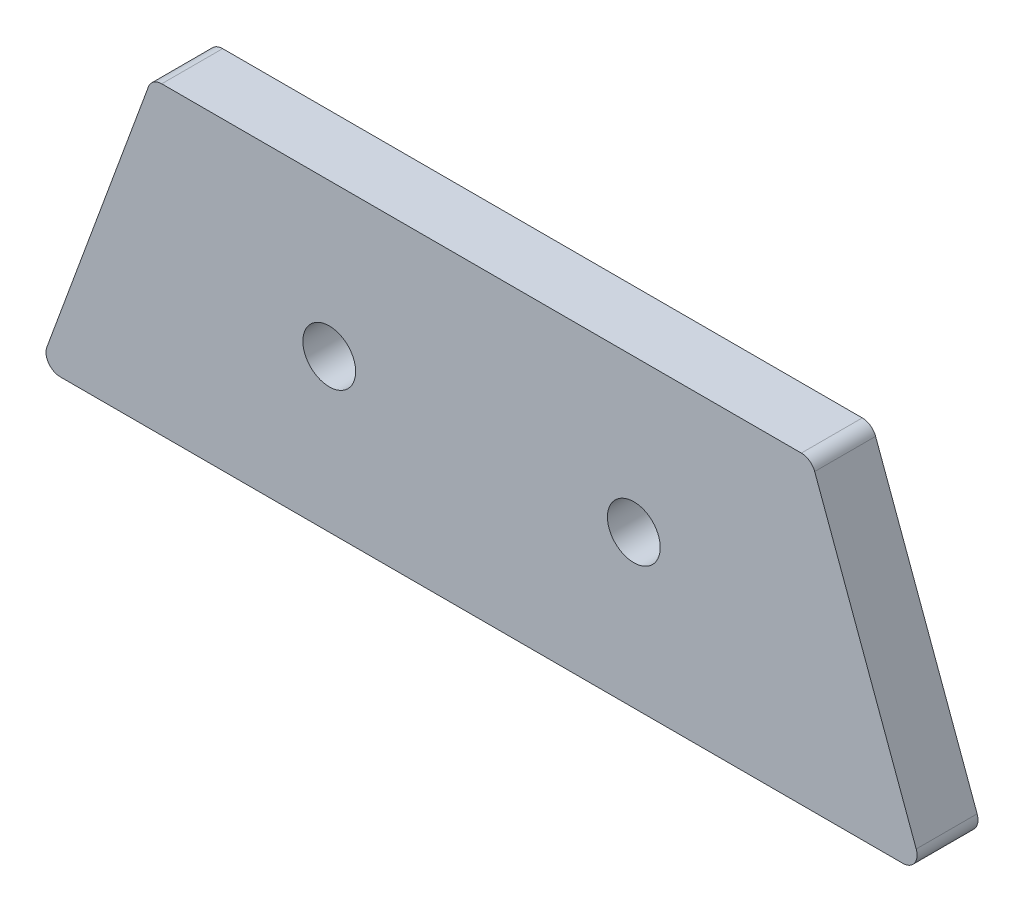
SolidWorks part; units mm, degrees
ref_plane "Front Plane" through (0, 0, 0) normal (0, 0, 1) x (1, 0, 0)
ref_plane "Top Plane" through (0, 0, 0) normal (0, 1, 0) x (1, 0, 0)
ref_plane "Right Plane" through (0, 0, 0) normal (1, 0, 0) x (0, 0, -1)
sketch "Sketch2" plane through (0, 0, 0) normal (0, 0, 1) x (1, 0, 0)
  line L0 (0, 84.074) -> (0, -72.39) construction
  line L1 (40.005, 34.1945) -> (-40.005, 34.1945)
  line L2 (52.705, -3.9055) -> (-52.705, -3.9055)
  line L3 (-54.3738, -1.514) -> (-41.6738, 33.03)
  line L4 (54.3738, -1.514) -> (41.6738, 33.03)
  arc A0 (-54.3738, -1.514) -> (-52.705, -3.9055) centre (-52.705, -2.1275) ccw
  arc A1 (-40.005, 34.1945) -> (-41.6738, 33.03) centre (-40.005, 32.4165) ccw
  arc A2 (54.3738, -1.514) -> (52.705, -3.9055) centre (52.705, -2.1275) cw
  arc A3 (40.005, 34.1945) -> (41.6738, 33.03) centre (40.005, 32.4165) cw
  circle A4 centre (-19.05, 15.1445) radius 3.302
  circle A5 centre (19.05, 15.1445) radius 3.302
  point P4 (0, 57.6776)
  point P9 (0, 19.5776)
  point P13 (-38.7967, 8.1836)
  point P20 (0, -3.9055)
  dimension "D2" = 3.556
  dimension "D3" = 3.556
  dimension "D6" = 6.604
  dimension "D1" = 38.1
  dimension "D4" = 105.41
  dimension "D5" = 80.01
  dimension "D7" = 19.05
  dimension "D8" = 19.05
extrude "Boss-Extrude1" add sketch "Sketch2" along normal blind 7.62
